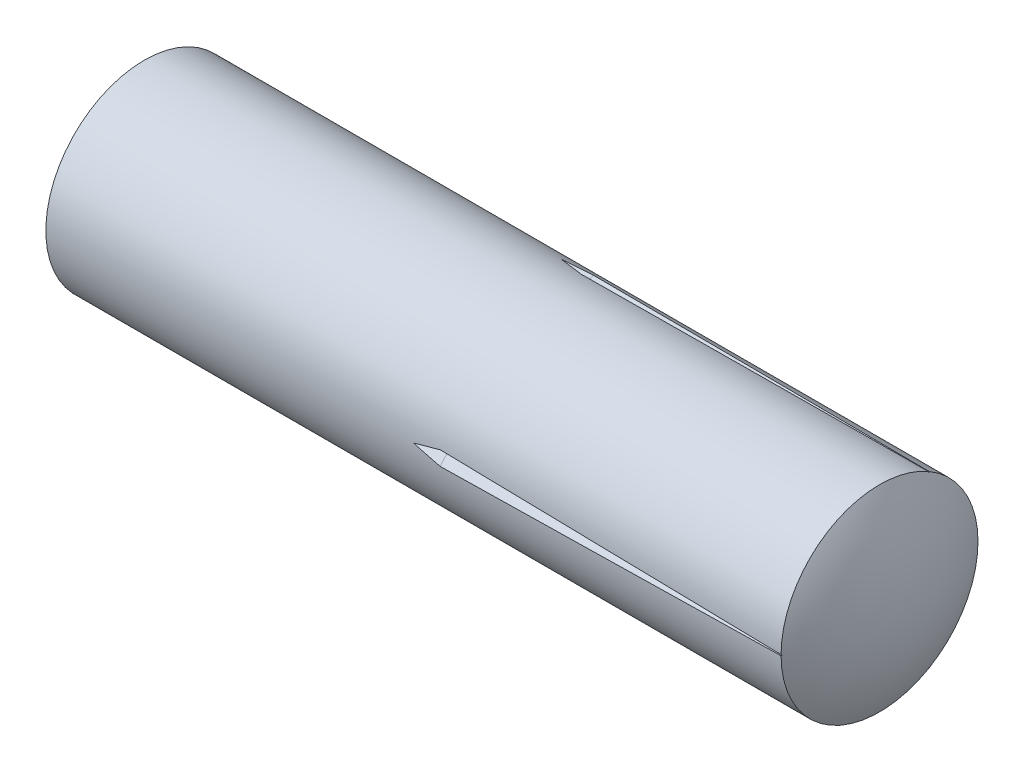
SolidWorks part; units mm, degrees
ref_plane "Plane1" through (0, 0, 0) normal (0, 0, 1) x (1, 0, 0)
ref_plane "Plane2" through (0, 0, 0) normal (0, 1, 0) x (1, 0, 0)
ref_plane "Plane3" through (0, 0, 0) normal (1, 0, 0) x (0, 0, -1)
sketch "Sketch1" plane through (0, 0, 0) normal (0, 0, 1) x (1, 0, 0)
  line L0 (-57, 0) -> (60, 0) construction
  line L1 (-50, 0) -> (-50, 1.25)
  line L2 (-46.6819, 12.5) -> (46.6506, 12.5)
  line L3 (-50, 0) -> (50, 0)
  arc A0 (-46.6819, 12.5) -> (-50, 1.25) centre (-25.0313, 0) ccw
  arc A1 (50, 0) -> (46.6506, 12.5) centre (25, 0) ccw
  dimension "D1" = 25
  dimension "D2" = 25
  dimension "Length" = 100
  dimension "D3" = 2.5
revolve "Base-Revolve" add sketch "Sketch1" angle 360 about L0
sketch "Sketch2" plane through (0, 0, 0) normal (1, 0, 0) x (0, 0, -1)
  line L0 (0, 0) -> (-14, 0) construction
  line L1 (-12.5, 0) -> (-14.3784, 1.3152)
  line L2 (-12.5, 0) -> (-14.3784, -1.3152)
  line L3 (-14.3784, -1.3152) -> (-14.3784, 1.3152)
  circle A0 centre (0, 0) radius 12.5 construction
  dimension "D1" = 25
  dimension "D2" = 70
  dimension "D3" = 35
  dimension "D4" = 1.8784
sketch "Sketch3" plane through (0, 0, 0) normal (0, 1, 0) x (1, 0, 0)
  line L0 (0, 0) -> (50, 0) construction
  line L1 (-57, 0) -> (60, 0) construction
  line L2 (0, -12.5) -> (3.125, -11.25)
  line L3 (3.125, -11.25) -> (50, -12.5)
  dimension "D2" = 25
  dimension "D1" = 50
  dimension "D3" = 22.5
  dimension "D4" = 25
  dimension "D5" = 3.125
sweep "Cut-Sweep1" cut profiles "Sketch2" path "Sketch3"
pattern_circular "CirPattern1" count 3 over 360 about axis through (-57, 0, 0) along (1, 0, 0) of "Cut-Sweep1"
equation "\"D1@Sketch1\" = \"Diameter@Sketch1\""
equation "\"D2@Sketch1\" = \"Diameter@Sketch1\""
equation "\"D3@Sketch1\" = \"Diameter@Sketch1\" * .1"
equation "\"D1@Sketch2\" = \"Diameter@Sketch1\""
equation "\"D3@Sketch2\" = \"D2@Sketch2\" / 2"
equation "\"D1@Sketch3\" = \"Length@Sketch1\" / 2"
equation "\"D2@Sketch3\" = \"Diameter@Sketch1\""
equation "\"D3@Sketch3\" = \"Diameter@Sketch1\" * .9"
equation "\"D4@Sketch3\" = \"Diameter@Sketch1\""
equation "\"D5@Sketch3\" = \"D1@Sketch1\" / 8"
